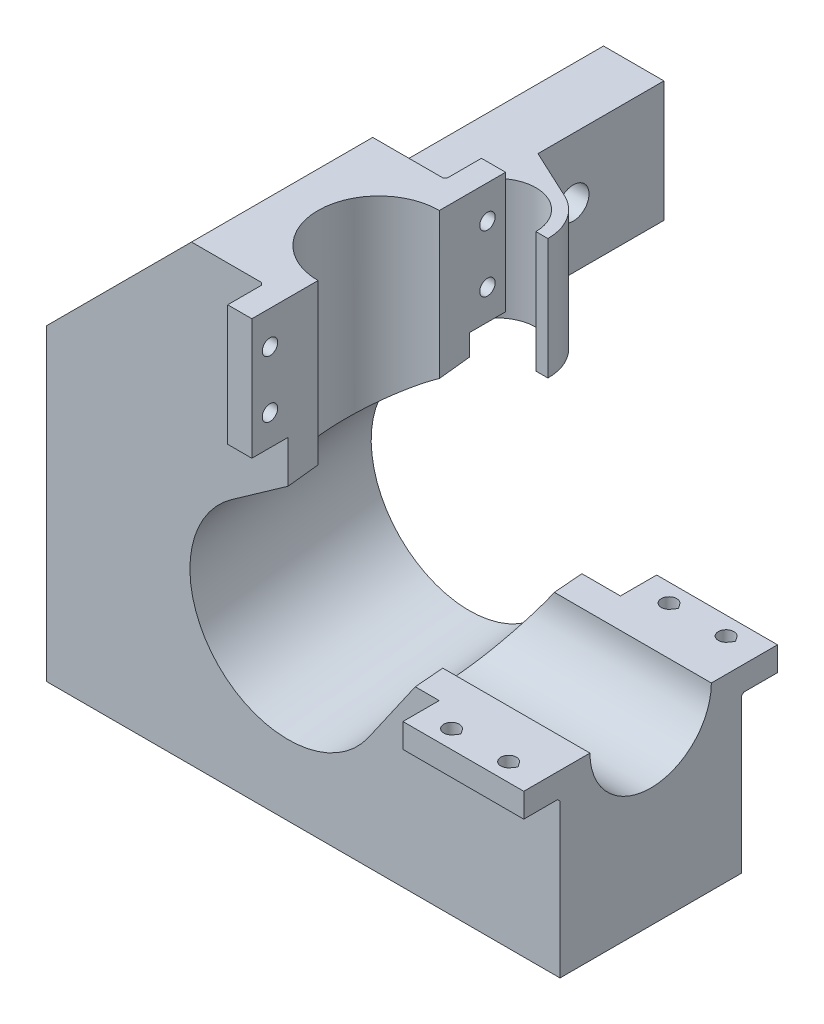
SolidWorks part; units mm, degrees
material "Custom Plastic"
ref_plane "X-Y Datum" through (0, 0, 0) normal (0, 0, 1) x (1, 0, 0)
ref_plane "X-Z Datum" through (0, 0, 0) normal (0, 1, 0) x (1, 0, 0)
ref_plane "Y-Z Datum" through (0, 0, 0) normal (1, 0, 0) x (0, 0, -1)
sketch "Sketch3" plane through (0, 0, 0) normal (0, 1, 0) x (1, 0, 0)
  line L0 (8.001, 0) -> (-8.001, 0) construction
  line L1 (0, 8.001) -> (0, -8.001) construction
  line L2 (8.001, 0) -> (10.541, 0)
  line L3 (-8.001, 0) -> (-10.541, 0) construction
  line L4 (-5.969, 8.6881) -> (-5.969, -8.6881) construction
  line L5 (0, 8.001) -> (0, 21.844) construction
  line L6 (0, -8.001) -> (0, -21.844) construction
  line L7 (-5.969, -8.6881) -> (-5.969, -21.844) construction
  line L8 (0, 21.844) -> (-5.969, 21.844) construction
  line L9 (-5.969, 8.6881) -> (-5.969, 21.844) construction
  line L10 (0, -21.844) -> (-5.969, -21.844) construction
  line L11 (-5.969, 21.844) -> (-18.669, 21.844) construction
  line L12 (-5.969, 0) -> (-18.669, 0)
  line L13 (-5.969, 0) -> (-5.969, 40.894)
  line L14 (-5.969, 40.894) -> (-18.669, 40.894)
  line L15 (-18.669, 0) -> (-18.669, 40.894)
  line L16 (4.4548, 9.5534) -> (-5.969, 14.4141)
  line L17 (-5.969, 0) -> (-18.669, 0)
  line L18 (-5.969, 0) -> (-5.969, -76.2)
  line L19 (-5.969, -76.2) -> (-18.669, -76.2)
  line L20 (-18.669, 0) -> (-18.669, -76.2)
  line L21 (-5.969, -21.844) -> (-18.669, -21.844) construction
  circle A0 centre (0, 0) radius 7.9375 construction
  circle A2 centre (0, 0) radius 8.001
  circle A3 centre (0, 0) radius 10.541
  point P4 (-7.9375, 0)
  point P7 (0, 0)
  point P8 (0, -7.9375)
  point P11 (0, 0)
  point P12 (7.9375, 0)
  point P13 (0, 7.9375)
  point P20 (-5.969, 0)
  point P28 (0, -10.541)
  point P29 (0, 10.541)
  dimension "D3" = 21.082
  dimension "D4" = 2.032
  dimension "D6" = 12.7
  dimension "D7" = 19.05
  dimension "D8" = 65
  dimension "D9" = 76.2
extrude "Boss-Extrude1" add sketch "Sketch3" along normal blind 12.7 and the other way blind 12.7 contours L17 A3 L18 A2 | L13 A3 L17 A2 | A3 L13 L14 L15 L12 | A3 L13 A2 L2 | A3 L12 L20 L19 L18 | A3 L16 L13 region at (2.9209, 0, -7.6588) region at (-8.2158, 0, -3.865) region at (-8.2158, 0, 3.865) region at (-3.3238, 0, -11.4774) region at (-12.452, 0, 39.1305) region at (-12.5734, 0, -21.4158)
sketch "Sketch5" plane through (-18.669, 0, 0) normal (-1, 0, 0) x (0, 0, 1)
  line L0 (0, -12.7) -> (0, 12.7) construction
  line L1 (-40.894, 12.7) -> (76.2, 12.7) construction
  circle A0 centre (-21.844, 0) radius 3.175 construction
  circle A1 centre (-21.844, 0) radius 3.302
  circle A2 centre (21.844, 0) radius 3.175 construction
  circle A3 centre (21.844, 0) radius 3.302
  point P0 (-21.844, 0)
  point P1 (21.844, 0)
  point P5 (0, 0)
  point P15 (0, 0)
  dimension "D1" = 6.35
  dimension "D2" = 6.604
  dimension "D3" = 6.35
  dimension "D4" = 6.604
extrude "Cut-Extrude1" cut sketch "Sketch5" against normal through all and the other way through all
ref_axis "Axis Chassis Tube X" through (110.7012, -6.6453, 57.15) along (-1, 0, 0)
ref_axis "Axis Chassis Tube Y" through (32.122, -70.0611, 57.15) along (0, 1, 0)
ref_point "Point Chassis Tube XYZ Intersection"
ref_axis "Axis Chassis Tube Z" through (32.122, 25.3343, -217.8748) along (0, -0.1155, 0.9933)
ref_plane "Plane Chassis Y" through (32.122, -6.6453, 57.15) normal (0, 1, 0) x (1, 0, 0)
ref_plane "Plane Chassis X" through (32.122, -6.6453, 57.15) normal (-1, 0, 0) x (0, 0, 1)
ref_plane "Plane Chassis Z" through (32.122, -6.6453, 57.15) normal (0, -0.1155, 0.9933) x (1, 0, 0)
sketch "Chassis Cutout Y Cross-section" plane through (32.122, -6.6453, 57.15) normal (0, 1, 0) x (1, 0, 0)
  circle A0 centre (0, 0) radius 12.7
sketch "Chassis Cutout Z Cross-section" plane through (32.122, -6.6453, 57.15) normal (0, -0.1155, 0.9933) x (1, 0, 0)
  circle A0 centre (0, 0) radius 12.7
sketch "Chassis Cutout X Cross-section" plane through (32.122, -6.6453, 57.15) normal (-1, 0, 0) x (0, 0, 1)
  line L0 (12.7, 0) -> (-12.7, 0) construction
  circle A0 centre (0, 0) radius 12.7
sketch "Sketch10" plane through (0, -12.7, 0) normal (0, -1, 0) x (1, 0, 0)
  line L0 (-18.669, 0) -> (-18.669, 76.2) construction
  line L1 (-18.669, 38.1) -> (-5.969, 38.1)
  line L2 (-18.669, 38.1) -> (-18.669, 76.2)
  line L3 (-18.669, 76.2) -> (-5.969, 76.2)
  line L4 (-5.969, 38.1) -> (-5.969, 76.2)
  dimension "D1" = 38.1
extrude "Boss-Extrude Arm FB Width" add sketch "Sketch10" along normal blind 44.45 from surface starting at plane "X-Z Datum"
sketch "Sketch12" plane through (-5.969, 0, 0) normal (1, 0, 0) x (0, 0, -1)
  line L6 (0, 0) -> (-76.2, 0) construction
  line L7 (-76.2, 0) -> (-38.1, 0)
  line L8 (-76.2, 0) -> (-76.2, -44.45)
  line L9 (-76.2, -44.45) -> (-38.1, -44.45)
  line L10 (-38.1, 0) -> (-38.1, -44.45)
  line L11 (-76.2, -44.45) -> (-76.2, 12.7) construction
  line M8 (-76.2, 12.7) -> (-76.2, -44.45)
  line M9 (-76.2, -44.45) -> (-38.1, -44.45)
  line M10 (-38.1, -44.45) -> (-38.1, -12.7)
sketch "Sketch13" plane through (0, 1.052, 58.045) normal (0, -0.1155, 0.9933) x (1, 0, 0)
  line L0 (49.0273, 4.088) -> (57.3158, -7.7492)
  line L1 (57.3158, -7.7492) -> (11.4845, -7.7492) construction
  line L2 (49.0273, -19.5864) -> (57.3158, -7.7492)
  line L3 (57.3158, -7.7492) -> (65.6042, 4.088)
  line L4 (65.6042, 4.088) -> (49.0273, 4.088)
  line L6 (32.122, -7.7492) -> (32.122, 17.4445) construction
  line L7 (20.2848, 9.1561) -> (32.122, 17.4445)
  line L8 (43.9592, 9.1561) -> (32.122, 17.4445)
  circle A0 centre (32.122, -7.7492) radius 12.7 construction
  circle A1 centre (32.122, -7.7492) radius 20.6375
  point P4 (32.122, -7.7492)
  dimension "D2" = 41.275
  dimension "D3" = 55
  dimension "D5" = 55
extrude "Boss-Extrude Arm Chassis FB" add sketch "Sketch12" along normal blind 95.25 contours L10 L7 M8 M9 M10 region at (-5.969, -22.225, 57.15)
sketch "Sketch15" plane through (0, 0, 0) normal (0, 1, 0) x (1, 0, 0)
  line L1 (-18.669, -76.2) -> (37.211, -76.2)
  line L2 (-18.669, -76.2) -> (-18.669, -38.1)
  line L3 (-18.669, -38.1) -> (37.211, -38.1)
  line L4 (37.211, -76.2) -> (37.211, -38.1)
  line L5 (89.281, -38.1) -> (-5.969, -38.1) construction
  line L6 (-18.669, 40.894) -> (-18.669, -76.2) construction
  dimension "D1" = 55.88
extrude "Boss-Extrude Arm Chassis LR" add sketch "Sketch15" along normal blind 50.8
sketch "Sketch16" plane through (32.122, -6.6453, 57.15) normal (-1, 0, 0) x (0, 0, 1)
  line L0 (-19.05, 0) -> (19.05, 0)
  line L1 (55, 0) -> (-55, 0) construction
  line L2 (19.05, 6.6453) -> (19.05, -37.8047) construction
  line L3 (-19.05, 12.7635) -> (19.05, 12.7635)
  line L4 (19.05, 57.4453) -> (19.05, 6.6453) construction
  line L5 (-19.05, 57.4453) -> (-19.05, 6.6453) construction
  line L6 (19.05, 12.7635) -> (19.05, 0)
  line L7 (-19.05, 12.7635) -> (-19.05, 0)
  line L8 (-19.05, 19.3453) -> (-19.05, -6.0547) construction
  circle A0 centre (0, 0) radius 12.7635
  point P10 (0, 0)
  point P15 (0, 12.7635)
  dimension "D1" = 25.527
extrude "Cut-Extrude Chassis FB" cut sketch "Sketch16" against normal through all contours A0 | A0 L3 L7 L0 | A0 L0 L6 L3 | A0 region at (32.122, 0.8079, 71.2376) region at (32.122, -1.2284, 57.15) region at (32.122, 0.8079, 43.0624)
sketch "Sketch17" plane through (32.122, -6.6453, 57.15) normal (0, 1, 0) x (1, 0, 0)
  line L1 (0, -19.05) -> (0, 19.05)
  line L2 (5.089, 19.05) -> (-50.791, 19.05) construction
  line L3 (-50.791, -19.05) -> (5.089, -19.05) construction
  line L4 (12.7635, -19.05) -> (12.7635, 19.05)
  line L5 (57.159, 19.05) -> (0, 19.05) construction
  line L6 (57.159, -19.05) -> (0, -19.05) construction
  line L9 (0, 19.05) -> (12.7635, 19.05)
  line L11 (57.159, 19.05) -> (0, 19.05) construction
  line L12 (0, -19.05) -> (12.7635, -19.05)
  circle A0 centre (0, 0) radius 12.7635
  point P17 (12.7635, 0)
  point P19 (0, 0)
  dimension "D1" = 25.527
extrude "Cut-Extrude Chassis LR" cut sketch "Sketch17" along normal through all contours A0 | A0 | A0 L4 | A0 L4 region at (39.5753, -6.6453, 71.2376) region at (26.705, -6.6453, 57.15) region at (37.539, -6.6453, 57.15) region at (39.5753, -6.6453, 43.0624)
extrude "Cut-Extrude Chassis Joint Clearance" cut sketch "Sketch13" against normal through all both and the other way through all contours A1 L2 L0 | A1 | A1 L8 L7 | L3 L4 L0 region at (53.7753, -6.6453, 57.15) region at (32.122, -6.6453, 57.15) region at (32.122, 14.863, 59.651)
sketch "Sketch19" plane through (0, 0, 76.2) normal (0, 0, 1) x (1, 0, 0)
  line L1 (89.281, -6.6453) -> (63.881, -6.6453)
  line L2 (89.281, -6.6453) -> (89.281, -11.7253)
  line L3 (89.281, -11.7253) -> (63.881, -11.7253)
  line L4 (63.881, -6.6453) -> (63.881, -11.7253)
  line M1 (89.281, -6.6453) -> (58.8564, -6.6453)
  line M7 (89.281, -44.45) -> (89.281, -6.6453)
  dimension "D2" = 5.08
extrude "Boss-Extrude FB Clamp Top" add sketch "Sketch19" along normal blind 7.62 from surface contours L4 L3 M1 M7 region at (76.581, -9.1853, 76.2) starting at face at (35.1677, -1.5499, 76.2)
extrude "Boss-Extrude FB Clamp Bottom" add sketch "Sketch19<3>" against normal blind 7.62 from surface starting at face at (20.3194, -0.0506, 38.1)
sketch "Sketch19<3>" plane through (0, 0, 76.2) normal (0, 0, 1) x (1, 0, 0) same geometry as "Sketch19"
sketch "Sketch20" plane through (0, 0, 76.2) normal (0, 0, 1) x (1, 0, 0)
  line L1 (32.122, 50.8) -> (27.042, 50.8)
  line L2 (32.122, 50.8) -> (32.122, 25.4)
  line L3 (32.122, 25.4) -> (27.042, 25.4)
  line L4 (27.042, 50.8) -> (27.042, 25.4)
  dimension "D2" = 5.08
extrude "Boss-Extrude LR Clamp Top" add sketch "Sketch20" along normal blind 7.62 from surface contours L2 L1 L4 L3 starting at face at (40.3883, -3.3999, 76.2)
extrude "Boss-Extrude LR Clamp Bottom" add sketch "Sketch20<3>" against normal blind 7.62 from surface starting at face at (26.1276, -1.6072, 38.1)
sketch "Sketch20<3>" plane through (0, 0, 76.2) normal (0, 0, 1) x (1, 0, 0) same geometry as "Sketch20"
sketch "Sketch23 LR Clamp Holes" plane through (32.122, 0, 0) normal (1, 0, 0) x (0, 0, -1)
  line L0 (-76.2, 50.8) -> (-76.2, 25.4) construction
  line L1 (-76.2, 25.4) -> (-76.2, 16.503) construction
  line L2 (-83.82, 25.4) -> (-76.2, 25.4) construction
  line L3 (-83.82, 43.8) -> (-76.2, 43.8) construction
  line L4 (-83.82, 50.8) -> (-83.82, 25.4) construction
  line L5 (-83.82, 50.8) -> (-69.9135, 50.8) construction
  line L6 (-83.82, 31.8) -> (-76.2, 31.8) construction
  line L7 (-83.82, 38.1) -> (-30.48, 38.1) construction
  line L8 (-38.1, 50.8) -> (-38.1, 25.4) construction
  line L9 (-38.1, 43.8) -> (-30.48, 43.8) construction
  line L10 (-30.48, 50.8) -> (-30.48, 25.4) construction
  line L11 (-38.1, 31.8) -> (-30.48, 31.8) construction
  line L12 (-57.15, 35.2176) -> (-57.15, 40.9824) construction
  line L13 (-30.48, 31.8) -> (-38.1, 31.8) construction
  line L14 (-30.48, 43.8) -> (-38.1, 43.8) construction
  circle A4 centre (-80.01, 43.8) radius 1.625
  circle A5 centre (-80.01, 31.8) radius 1.625
  circle A6 centre (-34.29, 31.8) radius 1.625
  circle A7 centre (-34.29, 43.8) radius 1.625
  point P11 (-80.01, 31.8)
  point P15 (-80.01, 43.8)
  point P36 (-57.15, 38.1)
  dimension "D2" = 3.25
  dimension "D5" = 3.25
  dimension "D1" = 7
  dimension "D3" = 12
  dimension "D4" = 3.81
sketch "Sketch26 FB Clamp Holes" plane through (0, -6.6453, 0) normal (0, 1, 0) x (1, 0, 0)
  line L0 (63.881, -76.2) -> (89.281, -76.2) construction
  line L1 (63.881, -38.1) -> (89.281, -38.1) construction
  line L2 (70.281, -80.01) -> (72.2648, -80.01) construction
  line L3 (82.281, -76.2) -> (82.281, -83.82) construction
  line L4 (71.6121, -79.0779) -> (72.2648, -80.01)
  line L5 (89.281, -83.82) -> (63.881, -83.82) construction
  line L6 (71.6121, -80.9421) -> (72.2648, -80.01)
  line L7 (76.581, -30.48) -> (76.581, -83.82) construction
  line L8 (70.281, -76.2) -> (70.281, -83.82) construction
  line L9 (63.881, -30.48) -> (89.281, -30.48) construction
  line L10 (89.281, -69.9135) -> (89.281, -83.82) construction
  line L11 (82.281, -80.01) -> (84.2648, -80.01) construction
  line L12 (83.6121, -79.0779) -> (84.2648, -80.01)
  line L13 (83.6121, -80.9421) -> (84.2648, -80.01)
  line L14 (84.719, -57.15) -> (68.443, -57.15) construction
  line L15 (70.281, -38.1) -> (70.281, -30.48) construction
  line L16 (71.6121, -33.3579) -> (72.2648, -34.29)
  line L17 (70.281, -34.29) -> (72.2648, -34.29) construction
  line L18 (71.6121, -35.2221) -> (72.2648, -34.29)
  line L19 (83.6121, -33.3579) -> (84.2648, -34.29)
  line L20 (82.281, -34.29) -> (84.2648, -34.29) construction
  line L21 (83.6121, -35.2221) -> (84.2648, -34.29)
  line L22 (82.281, -38.1) -> (82.281, -30.48) construction
  circle A4 centre (82.281, -80.01) radius 1.625
  circle A5 centre (70.281, -80.01) radius 1.625
  circle A6 centre (70.281, -34.29) radius 1.625
  circle A7 centre (82.281, -34.29) radius 1.625
  point P12 (82.281, -80.01)
  point P13 (70.281, -80.01)
  point P30 (76.581, -57.15)
  point P34 (76.581, -57.15)
  dimension "D5" = 3.25
  dimension "D3" = 12
  dimension "D4" = 3.81
  dimension "D1" = 3.25
  dimension "D2" = 7
  dimension "D6" = 55
  dimension "D7" = 55
chamfer "Chamfer1" distance 0.508 angle 45 2 edges at (76.581, -11.7253, 76.2) (76.581, -11.7253, 38.1)
chamfer "Chamfer2" distance 30.48 angle 45 1 edges at (-18.669, 50.8, 57.15)
chamfer "Chamfer7" distance 5.08 angle 45 2 edges at (-12.319, -12.7, 38.1) (-12.319, 12.7, 38.1)
extrude "Cut-Extrude7 FB Holes" cut sketch "Sketch26 FB Clamp Holes" against normal through all contours A5 | A5 L6 L4 | A4 L13 L12 | A4 | L19 A7 L21 | A7 | L16 A6 L18 | A6 region at (71.986, -6.6453, 80.01) region at (70.281, -6.6453, 80.01) region at (83.986, -6.6453, 80.01) region at (82.281, -6.6453, 80.01) region at (71.986, -6.6453, 34.29) region at (70.281, -6.6453, 34.29) region at (83.986, -6.6453, 34.29) region at (82.281, -6.6453, 34.29)
extrude "Cut-Extrude8 FB Holes" cut sketch "Sketch23 LR Clamp Holes" against normal through all
chamfer "Chamfer8" distance 0.508 angle 45 2 edges at (27.042, 38.1, 76.2) (27.042, 38.1, 38.1)
equation "\"Torsion Bar OD Clearance\"= 0.005"
equation "\"Torsion Bar OD Fit Size\"= 5 / 8in + \"Torsion Bar OD Clearance\""
equation "\"D2@Sketch3\"=\"Torsion Bar OD Fit Size\""
equation "\"TB Hook Thickness\"= 0.40"
equation "\"TB Hook OD\"= \"Torsion Bar OD Fit Size\" + \"TB Hook Thickness\" / 2"
equation "\"D3@Sketch3\"=\"TB Hook OD\""
equation "\"TB OD Clearance Depth\"= 0.080"
equation "\"D4@Sketch3\"=\"TB OD Clearance Depth\""
equation "\"Lower Jig thickness\"=0.5"
equation "\"D6@Sketch3\"=\"Lower Jig thickness\""
equation "\"Lower Jig Width\"= 1.0"
equation "\"D1@Boss-Extrude1\"=\"Lower Jig Width\"/2"
equation "\"D2@Boss-Extrude1\"=\"Lower Jig Width\"/2"
equation "\"Weld Stud OD\"= 0.25"
equation "\"Weld Stud Clearance\"= 0.01"
equation "\"D1@Sketch5\"=\"Weld Stud OD\""
equation "\"D2@Sketch5\"=\"Weld Stud OD\"+\"Weld Stud Clearance\""
equation "\"D3@Sketch5\"=\"Weld Stud OD\""
equation "\"D1@Chassis Cutout Y Cross-section\" = 1"
equation "\"D1@Chassis Cutout Z Cross-section\" = 1"
equation "\"D1@Chassis Cutout X Cross-section\" = 1"
equation "\"Chassis tube cut clearance diameter offset\"= 0.625"
equation "\"D2@Sketch13\"=\"Chassis tube cut clearance diameter offset\"+1"
equation "\"Arm height\"=1.5"
equation "\"D1@Sketch10\"=\"Arm height\""
equation "\"LR Arm length\"= 2.0"
equation "\"FB Arm length\"= 3.75"
equation "\"D1@Boss-Extrude Arm Chassis LR\" = \"LR Arm length\""
equation "\"D1@Boss-Extrude Arm Chassis FB\" = \"FB Arm length\""
equation "\"Chassis tube cut fit diameter offset\"= 0.005"
equation "\"D1@Sketch16\"=\"Chassis tube cut fit diameter offset\"+1"
equation "\"D1@Sketch17\"=\"Chassis tube cut fit diameter offset\"+1.0"
equation "\"FB Arm width\"= 1.75"
equation "\"D1@Boss-Extrude Arm FB Width\" = \"FB Arm width\""
equation "\"LR Arm width\"= 2.2"
equation "\"D1@Sketch15\"=\"LR Arm width\""
equation "\"FB Clamp Length\"= 1.0"
equation "\"Clamp Thickness\"= 0.20"
equation "\"Clamp Height\"= 0.30"
equation "\"D1@Sketch19\"=\"FB Clamp Length\""
equation "\"D2@Sketch19\"=\"Clamp Thickness\""
equation "\"D1@Boss-Extrude FB Clamp Top\" = \"Clamp Height\""
equation "\"D1@Boss-Extrude FB Clamp Bottom\" = \"Clamp Height\""
equation "\"LR Clamp Length\"= 1.0"
equation "\"D1@Sketch20\"=\"LR Clamp Length\""
equation "\"D2@Sketch20\"=\"Clamp Thickness\""
equation "\"D1@Boss-Extrude LR Clamp Top\" = \"Clamp Height\""
equation "\"D1@Boss-Extrude LR Clamp Bottom\" = \"Clamp Height\""
equation "\"Clamp hole diameter\"= 3.25mm'(3.25mm)"
equation "\"Clamp hole distance b/w\"= 12mm'(12mm)"
equation "\"D3@Sketch23 LR Clamp Holes\" = \"Clamp hole distance b/w\""
equation "\"Clamp hole dist. from edge\"= 7mm'(7mm)"
equation "\"D1@Sketch23 LR Clamp Holes\" = \"Clamp hole dist. from edge\""
equation "\"D1@Sketch26 FB Clamp Holes\"=\"Clamp hole diameter\""
equation "\"D2@Sketch26 FB Clamp Holes\"=\"Clamp hole dist. from edge\""
equation "\"D3@Sketch26 FB Clamp Holes\"=\"Clamp hole distance b/w\""
equation "\"D5@Sketch26 FB Clamp Holes\"=\"Clamp hole diameter\""
equation "\"D2@Sketch23 LR Clamp Holes\"=\"Clamp hole diameter\""
equation "\"D5@Sketch23 LR Clamp Holes\"=\"Clamp hole diameter\""
equation "\"Chassis Tube Cutout Offset\" = - 5.995"
